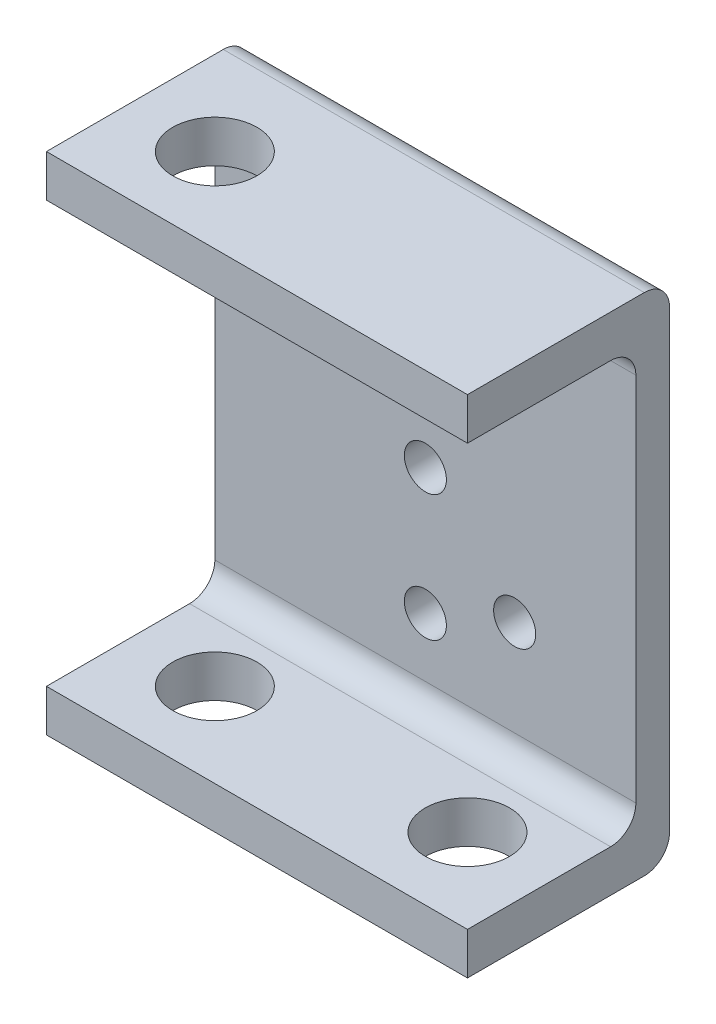
SolidWorks part; units mm, degrees
ref_plane "Front Plane" through (0, 0, 0) normal (0, 0, 1) x (1, 0, 0)
ref_plane "Top Plane" through (0, 0, 0) normal (0, 1, 0) x (1, 0, 0)
ref_plane "Right Plane" through (0, 0, 0) normal (1, 0, 0) x (0, 0, -1)
sketch "Sketch1" plane through (0, 0, 0) normal (1, 0, 0) x (0, 0, -1)
  line L0 (0, 27) -> (0, -27)
  line L1 (-3, 30) -> (-24, 30)
  line L2 (-24, 30) -> (-24, 25)
  line L3 (-24, 25) -> (-7, 25)
  line L4 (-4, 22) -> (-4, -22)
  line L5 (-7, -25) -> (-24, -25)
  line L6 (-24, -25) -> (-24, -30)
  line L7 (-24, -30) -> (-3, -30)
  arc A0 (-4, -22) -> (-7, -25) centre (-7, -22) cw
  arc A1 (-7, 25) -> (-4, 22) centre (-7, 22) cw
  arc A2 (0, -27) -> (-3, -30) centre (-3, -27) cw
  arc A3 (0, 27) -> (-3, 30) centre (-3, 27) ccw
  point P3 (0, 0)
  point P4 (0, 0)
  point P12 (0, 30)
  point P13 (0, 0)
  point P15 (-4, -25)
  point P18 (-4, 25)
  point P23 (0, 30)
  point P24 (0, 0)
  dimension "D7" = 3
  dimension "D8" = 3
  dimension "D9" = 3
  dimension "D1" = 60
  dimension "D2" = 50
  dimension "D3" = 5
  dimension "D4" = 4
  dimension "D5" = 20
  dimension "D6" = 24
extrude "Boss-Extrude1" add sketch "Sketch1" along normal mid plane 50
sketch "Sketch2" plane through (0, 0, 0) normal (0, 0, -1) x (-1, 0, 0)
  line L0 (0, 0) -> (0, 15) construction
  line L1 (0, 0) -> (10.6066, 10.6066) construction
  line L2 (0, 0) -> (-10.6066, -10.6066) construction
  line L3 (0, 0) -> (0, -15) construction
  circle A0 centre (0, 0) radius 2.5
  circle A1 centre (0, 15) radius 2.5
  circle A2 centre (10.6066, 10.6066) radius 2.5
  circle A3 centre (-10.6066, -10.6066) radius 2.5
  circle A4 centre (0, -15) radius 2.5
  point P10 (0, 0)
  dimension "D1" = 5
  dimension "D3" = 45
  dimension "D2" = 15
  dimension "D4" = 135
extrude "Cut-Extrude1" cut sketch "Sketch2" against normal blind 4
sketch "Sketch5" plane through (0, -30, 0) normal (0, -1, 0) x (1, 0, 0)
  line L0 (-15, 14) -> (15, 14) construction
  line L2 (0, 14) -> (0, 0) construction
  line L4 (-25, 24) -> (-25, 3) construction
  line L5 (25, 24) -> (-25, 24) construction
  circle A0 centre (-15, 14) radius 5
  circle A1 centre (15, 14) radius 5
  point P9 (-3.386, 20.5725)
  dimension "D1" = 10
  dimension "D2" = 10
  dimension "D3" = 10
extrude "Cut-Extrude2" cut sketch "Sketch5" against normal up to surface (60 mm away) contours A0 up to face at (0, 30, 13.5)
extrude "Cut-Extrude3" cut sketch "Sketch5<3>" against normal up to surface (5 mm away) contours A1 up to face at (-15, -25, 9)
sketch "Sketch5<3>" plane through (0, -30, 0) normal (0, -1, 0) x (1, 0, 0) same geometry as "Sketch5"
